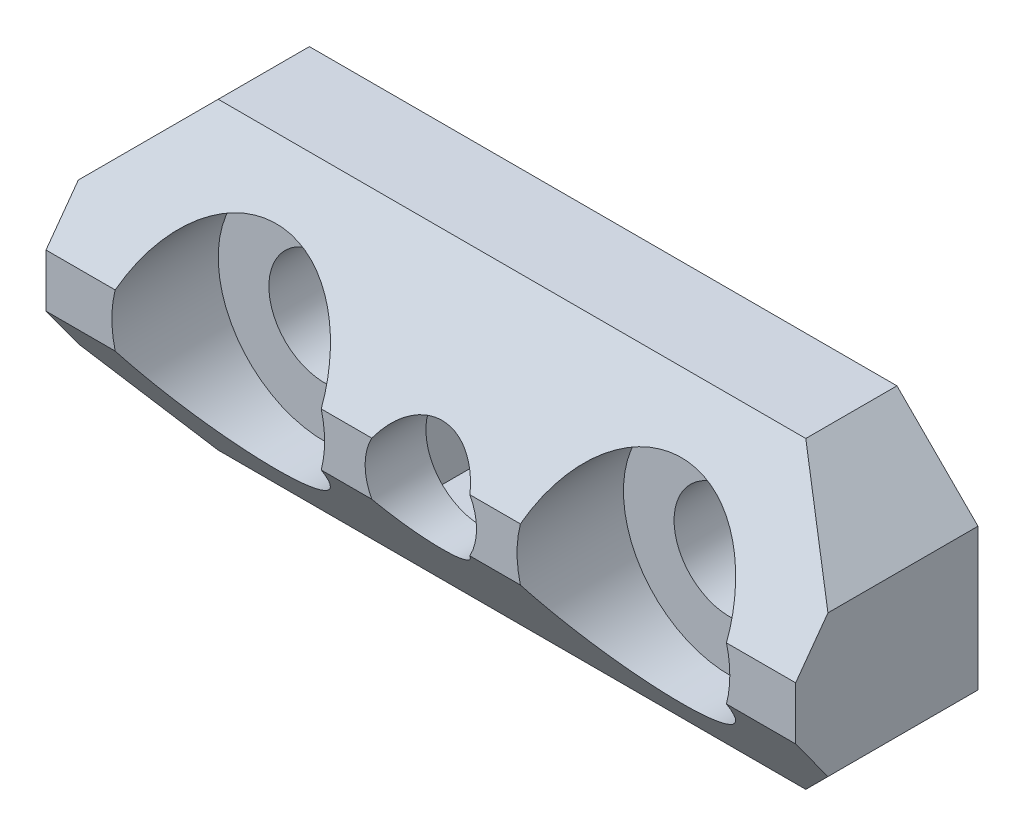
SolidWorks part; units mm, degrees
ref_plane "Front Plane" through (0, 0, 0) normal (0, 0, 1) x (1, 0, 0)
ref_plane "Top Plane" through (0, 0, 0) normal (0, 1, 0) x (1, 0, 0)
ref_plane "Right Plane" through (0, 0, 0) normal (1, 0, 0) x (0, 0, -1)
sketch "Sketch1" plane through (0, 0, 0) normal (0, 0, 1) x (1, 0, 0)
  line L0 (-10, 0) -> (10, 0) construction
  line L1 (-18.5, -7.5) -> (18.5, -7.5)
  line L2 (-18.5, -7.5) -> (-18.5, 7.5)
  line L3 (-18.5, 7.5) -> (18.5, 7.5)
  line L4 (18.5, -7.5) -> (18.5, 7.5)
  line L5 (-18.5, -7.5) -> (18.5, 7.5) construction
  line L6 (-18.5, 7.5) -> (18.5, -7.5) construction
  point P0 (0, 0)
  point P8 (0, 0)
  dimension "D1" = 37
  dimension "D2" = 15
  dimension "D3" = 20
extrude "Boss-Extrude1" add sketch "Sketch1" along normal blind 9
hole_wizard "CBORE for M5 SBHCS2" positions "Sketch2" profile "Sketch3" counterbore size "M5" standard "ANSI Metric" end condition through all
sketch "Sketch2" plane through (0, 0, 9) normal (0, 0, 1) x (1, 0, 0)
  point P0 (-10, 0)
  point P3 (10, 0)
sketch "Sketch3" plane through (-10, 0, 9) normal (1, 0, 0) x (0, -1, 0)
  line L0 (0, 0) -> (0, 9)
  line L1 (0, 9) -> (2.75, 9)
  line L3 (2.75, 9) -> (2.75, 5.25)
  line L4 (2.75, 5.25) -> (5.25, 5.25)
  line L5 (5.25, 5.25) -> (5.25, 0)
  line L7 (5.25, 0) -> (0, 0)
  line L11 (0, -6.35) -> (0, 107.95) construction
  dimension "Thru Hole Dia." = 5.5
  dimension "Thru Hole Depth" = 9
  dimension "C'Bore Dia." = 10.5
  dimension "C'Bore Depth" = 5.25
hole_wizard "M5 Clearance Hole1" positions "Sketch4" profile "Sketch5" hole size "M5" standard "ANSI Metric" end condition through all
sketch "Sketch4" plane through (0, 0, 9) normal (0, 0, 1) x (1, 0, 0)
  point P0 (0, 0)
sketch "Sketch5" plane through (0, 0, 9) normal (1, 0, 0) x (0, -1, 0)
  line L0 (0, 0) -> (0, 9)
  line L1 (0, 9) -> (2.75, 9)
  line L2 (2.75, 9) -> (2.75, 0)
  line L5 (2.75, 0) -> (0, 0)
  line L11 (0, -6.35) -> (0, 107.95) construction
  dimension "Thru Hole Dia." = 5.5
  dimension "Thru Hole Depth" = 9
sketch "Sketch6" plane through (0, 0, 0) normal (0, 0, -1) x (-1, 0, 0)
  line L1 (-4.5, -4.5) -> (4.5, -4.5)
  line L2 (-4.5, -4.5) -> (-4.5, 4.5)
  line L3 (-4.5, 4.5) -> (4.5, 4.5)
  line L4 (4.5, -4.5) -> (4.5, 4.5)
  line L5 (-4.5, -4.5) -> (4.5, 4.5) construction
  line L6 (-4.5, 4.5) -> (4.5, -4.5) construction
  point P0 (0, 0)
  dimension "D1" = 9
extrude "Cut-Extrude1" cut sketch "Sketch6" against normal blind 6
chamfer "Chamfer1" distance 4.5 angle 54 2 edges at (0, -7.5, 9) (0, 7.5, 9) first distance on face at (0, -7.5, 4.5) first distance on face at (0, 7.5, 4.5)
chamfer "Chamfer2" distance 4 angle 45 4 edges at (18.5, 7.5, 2.25) (18.5, -7.5, 2.25) (-18.5, -7.5, 2.25) (-18.5, 7.5, 2.25)
sketch "profile" plane through (18.5, 0, 0) normal (1, 0, 0) x (0, 0, -1)
  line L0 (-7.4062, -3.5) -> (-4.5, -7.5) construction
  line L1 (-4.5, -7.5) -> (0, -7.5) construction
  line L2 (0, -7.5) -> (0, -3.5) construction
  line L3 (0, -3.5) -> (0, 3.5) construction
  line L4 (-7.4062, 3.5) -> (-9, 1.3063) construction
  line L5 (-9, 1.3063) -> (-9, -1.3063) construction
  line L6 (-9, -1.3063) -> (-7.4062, -3.5) construction
  line L7 (-4.5, 7.5) -> (-7.4062, 3.5) construction
  line L8 (0, 3.5) -> (0, 7.5) construction
  line L9 (0, 7.5) -> (-4.5, 7.5) construction
  line L10 (-7.4062, -3.5) -> (-4.5, -7.5)
  line L11 (-4.5, -7.5) -> (0, -7.5)
  line L12 (0, -7.5) -> (0, -3.5)
  line L13 (0, -3.5) -> (0, 3.5)
  line L14 (-7.4062, 3.5) -> (-9, 1.3063)
  line L15 (-9, 1.3063) -> (-9, -1.3063)
  line L16 (-9, -1.3063) -> (-7.4062, -3.5)
  line L17 (-4.5, 7.5) -> (-7.4062, 3.5)
  line L18 (0, 3.5) -> (0, 7.5)
  line L19 (0, 7.5) -> (-4.5, 7.5)
  dimension "D1" = 4.5
  dimension "D2" = 54
  dimension "D3" = 2.6126
